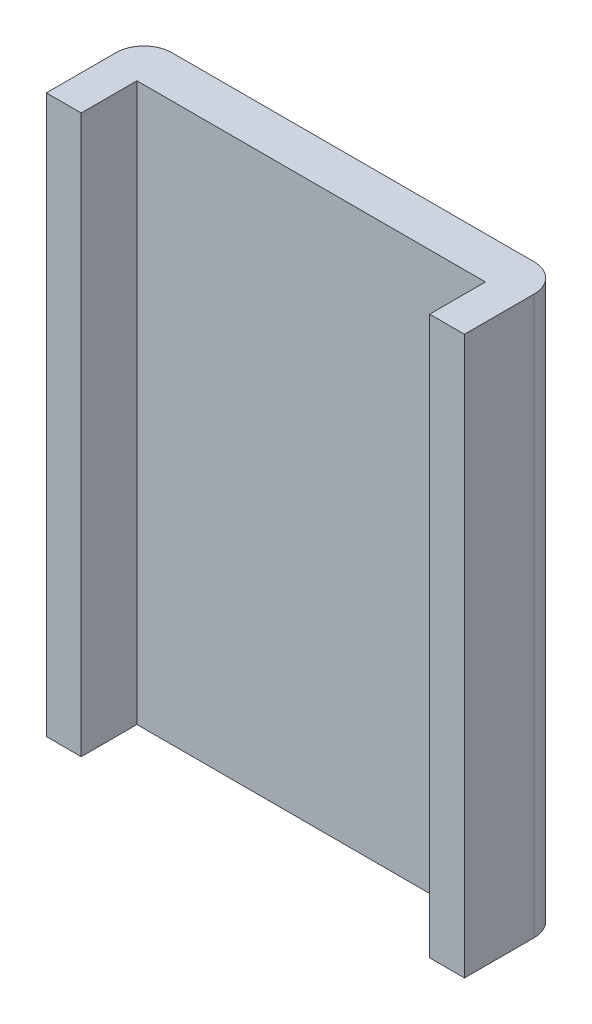
SolidWorks part; units mm, degrees
ref_plane "Front Plane" through (0, 0, 0) normal (0, 0, 1) x (1, 0, 0)
ref_plane "Top Plane" through (0, 0, 0) normal (0, 1, 0) x (1, 0, 0)
ref_plane "Right Plane" through (0, 0, 0) normal (1, 0, 0) x (0, 0, -1)
sketch "Sketch1" plane through (0, 0, 0) normal (0, 0, 1) x (1, 0, 0)
  line L1 (-3.75, 5) -> (3.75, 5)
  line L2 (-3.75, 5) -> (-3.75, -5)
  line L3 (-3.75, -5) -> (3.75, -5)
  line L4 (3.75, 5) -> (3.75, -5)
  line L5 (-3.75, 5) -> (3.75, -5) construction
  line L6 (-3.75, -5) -> (3.75, 5) construction
  line L7 (-3.125, 5) -> (3.125, 5)
  line L8 (-3.125, 5) -> (-3.125, -5)
  line L9 (-3.125, -5) -> (3.125, -5)
  line L10 (3.125, 5) -> (3.125, -5)
  line L11 (-3.125, 5) -> (3.125, -5) construction
  line L12 (-3.125, -5) -> (3.125, 5) construction
  point P0 (0, 0)
  point P6 (0, 0)
  dimension "D1" = 7.5
  dimension "D2" = 10
  dimension "D3" = 10
  dimension "D4" = 6.25
extrude "Boss-Extrude1" add sketch "Sketch1" along normal blind 0.75 contours L10 L1 L8 L3 region at (0, 0, 0)
extrude "Boss-Extrude2" add sketch "Sketch1<3>" along normal blind 1.75 contours L1 L10 L3 L4 | L8 L1 L2 L3 region at (-3.4375, 0, 0) region at (3.4375, 0, 0)
sketch "Sketch1<3>" plane through (0, 0, 0) normal (0, 0, 1) x (1, 0, 0) same geometry as "Sketch1"
ref_axis "Axis1" through (0, 0, -4.7229) along (0, 0, 1)
ref_plane "Plane1" through (0, 0, 0) normal (0.9659, 0.2588, 0) x (0, 0, 1)
ref_plane "Plane2" through (0, 0, 0) normal (0.9659, -0.2588, 0) x (0, 0, 1)
fillet "Fillet1" radius 0.5 2 edges at (-3.75, 0, 0) (3.75, 0, 0)
equation "\"D3@Sketch1\"=\"D2@Sketch1\""
